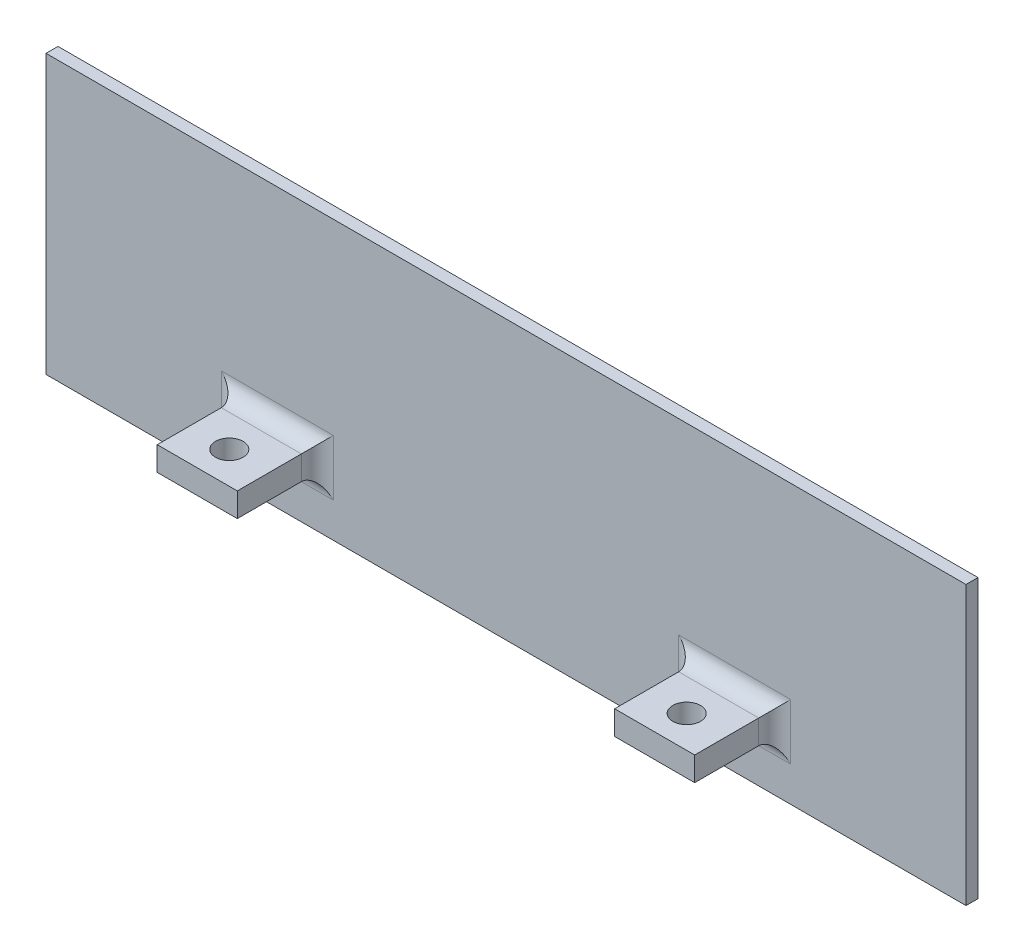
SolidWorks part; units mm, degrees
ref_plane "Front Plane" through (0, 0, 0) normal (0, 0, 1) x (1, 0, 0)
ref_plane "Top Plane" through (0, 0, 0) normal (0, 1, 0) x (1, 0, 0)
ref_plane "Right Plane" through (0, 0, 0) normal (1, 0, 0) x (0, 0, -1)
sketch "Sketch1" plane through (0, 0, 0) normal (0, 0, 1) x (1, 0, 0)
  line L0 (-57.475, 21.7589) -> (-57.475, -12.9911) construction
  line L1 (-57.475, -12.9911) -> (57.475, -12.9911)
  line L2 (-57.475, -12.9911) -> (-57.475, 21.7589)
  line L3 (-57.475, 21.7589) -> (57.475, 21.7589)
  line L4 (57.475, -12.9911) -> (57.475, 21.7589)
  line L5 (-57.475, -12.9911) -> (57.475, 21.7589) construction
  line L6 (-57.475, 21.7589) -> (57.475, -12.9911) construction
  line L7 (-57.475, -12.9911) -> (57.475, -12.9911) construction
  line L9 (57.475, 21.7589) -> (57.475, -12.9911) construction
  line L10 (-57.475, 21.7589) -> (57.475, 21.7589) construction
  point P0 (0, 0)
extrude "RearPanel" add sketch "Sketch1" along normal blind 1.5
sketch "Sketch2" plane through (0, 0, 1.5) normal (0, 0, 1) x (1, 0, 0)
  line L0 (23.575, -3.6411) -> (33.575, -3.6411)
  line L1 (-33.575, -3.6411) -> (-23.575, -3.6411)
  line L2 (-33.575, -3.6411) -> (-33.575, -6.6411)
  line L3 (-33.575, -6.6411) -> (-23.575, -6.6411)
  line L4 (-23.575, -3.6411) -> (-23.575, -6.6411)
  line L9 (23.575, -3.6411) -> (23.575, -6.6411)
  line L10 (23.575, -6.6411) -> (33.575, -6.6411)
  line L11 (33.575, -3.6411) -> (33.575, -6.6411)
  line L12 (-57.475, -12.9911) -> (57.475, -12.9911) construction
  line L16 (-28.575, -14.0652) -> (28.575, -14.0652) construction
  point P10 (0, -14.0652)
  point P12 (-28.575, -3.6411)
  point P15 (28.575, -3.6411)
  dimension "D1" = 10
  dimension "D2" = 3
  dimension "D3" = 6.35
  dimension "D4" = 57.15
extrude "ScrewMounts" add sketch "Sketch2" along normal blind 10
fillet "Fillet1" radius 2 8 edges at (-28.575, -3.6411, 1.5) (23.575, -5.1411, 1.5) (28.575, -3.6411, 1.5) (33.575, -5.1411, 1.5) (28.575, -6.6411, 1.5) (-23.575, -5.1411, 1.5) (-33.575, -5.1411, 1.5) (-28.575, -6.6411, 1.5)
sketch "Sketch3" plane through (0, -3.6411, 0) normal (0, 1, 0) x (1, 0, 0)
  line L0 (-33.575, -7.5) -> (-23.575, -7.5) construction
  line L1 (-33.575, -11.5) -> (-33.575, -3.5) construction
  line L2 (-23.575, -11.5) -> (-23.575, -3.5) construction
  line L4 (23.575, -7.5) -> (33.575, -7.5) construction
  line L5 (23.575, -11.5) -> (23.575, -3.5) construction
  line L6 (33.575, -11.5) -> (33.575, -3.5) construction
  point P16 (-28.575, -7.5)
  point P18 (28.575, -7.5)
hole_wizard "#4 Clearance Hole1" positions "Sketch3" profile "Sketch4" hole size "#4" standard "ANSI Inch" end condition through all
sketch "Sketch4" plane through (28.575, -3.6411, 7.5) normal (1, 0, 0) x (0, 0, 1)
  line L0 (0, 0) -> (0, 9.35)
  line L1 (0, 9.35) -> (1.7272, 9.35)
  line L2 (1.7272, 9.35) -> (1.7272, 0)
  line L5 (1.7272, 0) -> (0, 0)
  line L11 (0, -6.35) -> (0, 107.95) construction
  dimension "Thru Hole Dia." = 3.4544
  dimension "Thru Hole Depth" = 9.35
ref_axis "Axis1" through (-28.575, -6.6411, 7.5) along (0, 1, 0)
ref_axis "Axis2" through (28.575, -6.6411, 7.5) along (0, 1, 0)
ref_plane "MidPlane" through (0, 0, 0) normal (1, 0, 0) x (0, 0, -1)
